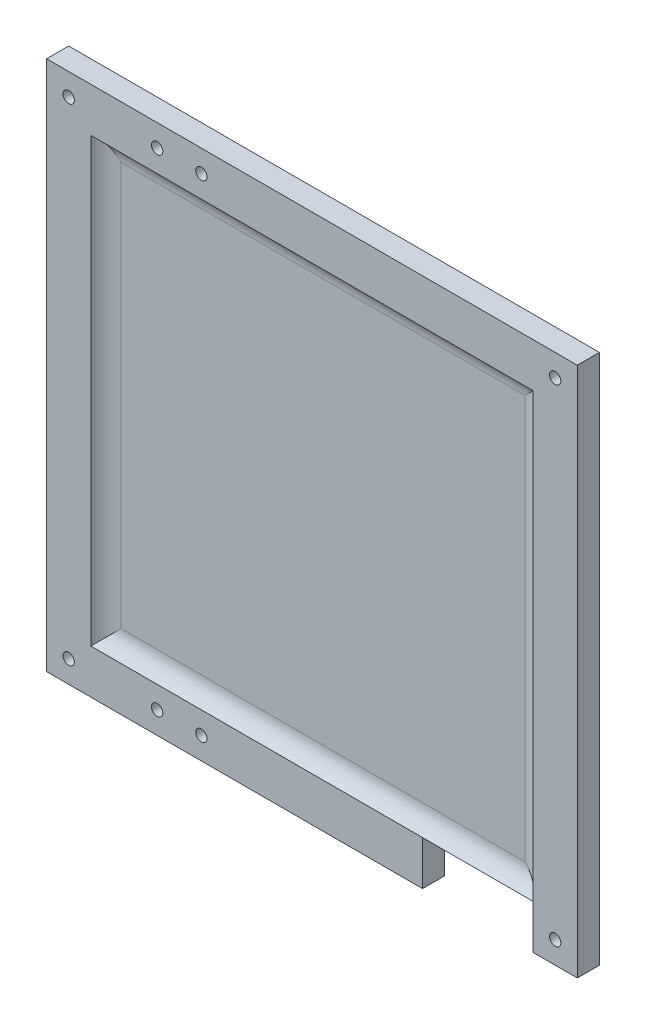
SolidWorks part; units mm, degrees
ref_plane "Front Plane" through (0, 0, 0) normal (0, 0, 1) x (1, 0, 0)
ref_plane "Top Plane" through (0, 0, 0) normal (0, 1, 0) x (1, 0, 0)
ref_plane "Right Plane" through (0, 0, 0) normal (1, 0, 0) x (0, 0, -1)
sketch "Sketch1" plane through (0, 0, 0) normal (0, 0, 1) x (1, 0, 0)
  line L0 (-120, 110) -> (120, 110) construction
  line L1 (-120, -120) -> (120, -120)
  line L2 (-120, -120) -> (-120, 120)
  line L3 (-120, 120) -> (120, 120)
  line L4 (120, -120) -> (120, 120)
  line L5 (-120, -120) -> (120, 120) construction
  line L6 (-120, 120) -> (120, -120) construction
  line L7 (0, 120) -> (0, -120) construction
  line L8 (-120, 0) -> (120, 0) construction
  line L9 (-70, 120) -> (-70, -120) construction
  line L10 (-50, 120) -> (-50, -120) construction
  circle A0 centre (-110, 110) radius 2.55
  circle A1 centre (110, 110) radius 2.55
  circle A2 centre (110, -110) radius 2.55
  circle A3 centre (-110, -110) radius 2.55
  circle A4 centre (-70, 110) radius 2.55
  circle A5 centre (-70, -110) radius 2.55
  circle A6 centre (-50, 110) radius 2.55
  circle A7 centre (-50, -110) radius 2.55
  point P0 (0, 0)
  point P30 (0, 0)
  dimension "D4" = 5.1
  dimension "D7" = 5.1
  dimension "D9" = 5.1
  dimension "D1" = 240
  dimension "D2" = 240
  dimension "D3" = 10
  dimension "D5" = 10
  dimension "D6" = 50
  dimension "D8" = 20
extrude "Boss-Extrude1" add sketch "Sketch1" along normal blind 10
sketch "Sketch2" plane through (0, 0, 10) normal (0, 0, 1) x (1, 0, 0)
  line L8 (100, -100) -> (100, 100)
  line L9 (-100, -100) -> (100, -100)
  line L10 (-100, 100) -> (-100, -100)
  line L11 (100, 100) -> (-100, 100)
  line L12 (100, -100) -> (100, 100)
  line L13 (-100, -100) -> (100, -100)
  line L14 (-100, 100) -> (-100, -100)
  line L15 (100, 100) -> (-100, 100)
  dimension "D1" = 20
extrude "Cut-Extrude1" cut sketch "Sketch2" against normal blind 5
fillet "Fillet1" radius 10 4 edges at (100, 0, 5) (0, -100, 5) (-100, 0, 5) (0, 100, 5)
sketch "Sketch3" plane through (0, 0, 10) normal (0, 0, 1) x (1, 0, 0)
  line L0 (-120, -120) -> (120, -120) construction
  line L1 (50, -120) -> (100, -120)
  line L2 (50, -120) -> (50, -100)
  line L3 (50, -100) -> (100, -100)
  line L4 (100, -120) -> (100, -100)
  line L5 (-100, -100) -> (100, -100) construction
  line L6 (120, -120) -> (120, 120) construction
  dimension "D1" = 50
  dimension "D2" = 20
extrude "Cut-Extrude2" cut sketch "Sketch3" against normal blind 150
